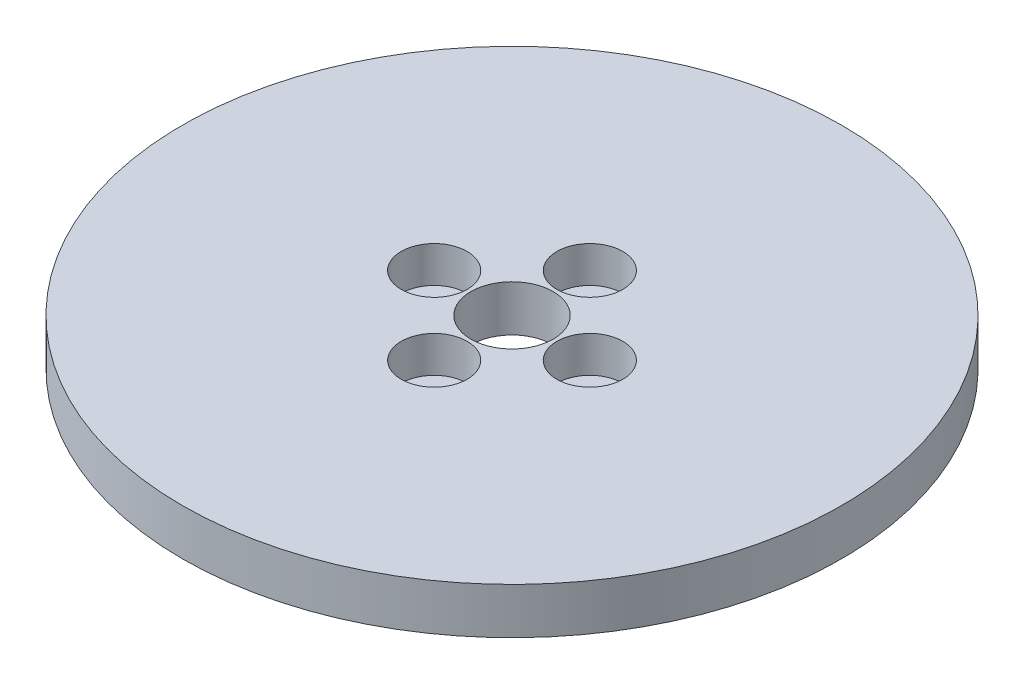
SolidWorks part; units mm, degrees
ref_plane "Front Plane" through (0, 0, 0) normal (0, 0, 1) x (1, 0, 0)
ref_plane "Top Plane" through (0, 0, 0) normal (0, 1, 0) x (1, 0, 0)
ref_plane "Right Plane" through (0, 0, 0) normal (1, 0, 0) x (0, 0, -1)
sketch "Sketch1" plane through (0, 0, 0) normal (0, 1, 0) x (1, 0, 0)
  circle A0 centre (0, 0) radius 100
  dimension "FLANGE_OD" = 200
extrude "Boss-Extrude1" add sketch "Sketch1" along normal blind 14
sketch "Sketch2" plane through (0, 0, 0) normal (0, 1, 0) x (1, 0, 0)
  circle A0 centre (0, 0) radius 12.5
  dimension "BORE_D" = 25
extrude "Cut-Extrude1" cut sketch "Sketch2" along normal through all
sketch "Sketch3" plane through (0, 14, 0) normal (0, 1, 0) x (1, 0, 0)
  circle A0 centre (0, 0) radius 23.6167 construction
  circle A1 centre (-23.6167, 0) radius 10
  dimension "BOLT_D" = 20
  dimension "BOLT_PCD" = 47.2334
extrude "Cut-Extrude2" cut sketch "Sketch3" against normal blind 11.0154
pattern_circular "CirPattern1" count 4 over 360 about axis through (0, 0, 0) along (0, 1, 0) of "Cut-Extrude2"
